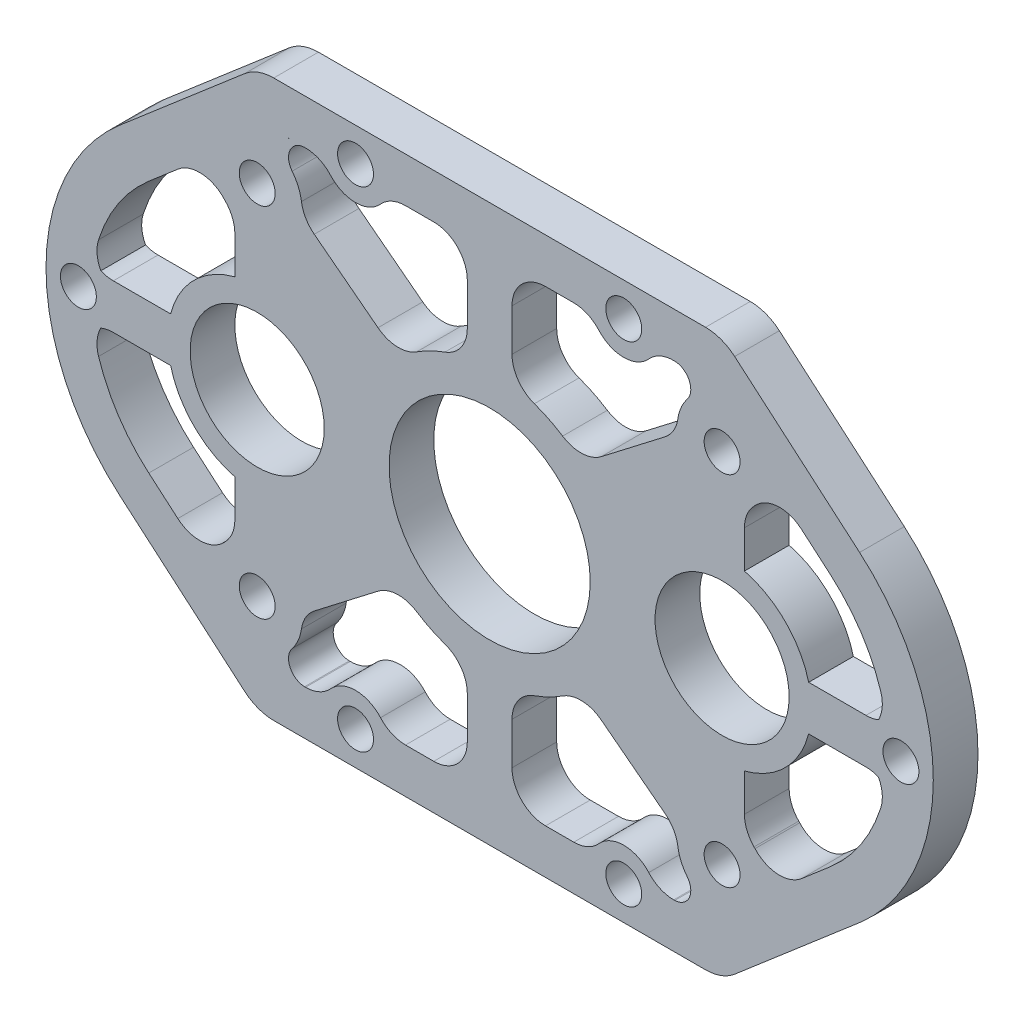
SolidWorks part; units mm, degrees
material "6061-T6 (SS)"
ref_plane "Front Plane" through (0, 0, 0) normal (0, 0, 1) x (1, 0, 0)
ref_plane "Top Plane" through (0, 0, 0) normal (0, 1, 0) x (1, 0, 0)
ref_plane "Right Plane" through (0, 0, 0) normal (1, 0, 0) x (0, 0, -1)
sketch "Sketch1" plane through (0, 0, 0) normal (0, 0, 1) x (1, 0, 0)
  line L0 (127, 25.4) -> (127, 0) construction
  line L1 (0, 0) -> (254, 0)
  line L2 (0, 0) -> (0, 25.4)
  line L3 (0, 25.4) -> (254, 25.4)
  line L4 (254, 0) -> (254, 25.4)
  line L18 (110.6338, 19.05) -> (106.9677, 12.7)
  line L19 (106.9677, 12.7) -> (110.6338, 6.35)
  line L20 (110.6338, 6.35) -> (117.9662, 6.35)
  line L21 (117.9662, 6.35) -> (121.6323, 12.7)
  line L22 (121.6323, 12.7) -> (117.9662, 19.05)
  line L23 (117.9662, 19.05) -> (110.6338, 19.05)
  circle A0 centre (81.28, 12.7) radius 30 construction
  circle A1 centre (147.32, 12.7) radius 30 construction
  circle A2 centre (81.28, 12.7) radius 7.62 construction
  circle A3 centre (147.32, 12.7) radius 8.636
  circle A4 centre (81.28, 12.7) radius 8.636
  circle A5 centre (147.32, 12.7) radius 7.62 construction
  circle A6 centre (114.3, 12.7) radius 25.4 construction
  circle A7 centre (114.3, 12.7) radius 26.67
  circle A8 centre (114.3, 12.7) radius 22.2377 construction
  circle A11 centre (114.3, 12.7) radius 6.35 construction
  point P46 (0, 12.7)
  dimension "D4" = 17.272
  dimension "D9" = 53.34
  dimension "D13" = 12.7
  dimension "D1" = 25.4
  dimension "D2" = 254
  dimension "D10" = 12.7
  dimension "D12" = 12.7
sketch "Sketch3" plane through (0, 0, 0) normal (0, 0, 1) x (1, 0, 0)
  line L0 (81.28, 42.7) -> (147.32, 42.7) construction
  line L5 (81.28, 12.7) -> (114.3, 12.7) construction
  line L6 (114.3, 12.7) -> (147.32, 12.7) construction
  line L9 (114.3, 42.7) -> (114.3, -17.3) construction
  line L10 (61.7477, 35.4704) -> (81.28, 52.225)
  line L25 (81.28, 52.225) -> (147.32, 52.225)
  line L26 (147.32, 52.225) -> (166.8523, 35.4704)
  line L27 (110.6338, 19.05) -> (106.9677, 12.7)
  line L28 (106.9677, 12.7) -> (110.6338, 6.35)
  line L29 (110.6338, 6.35) -> (117.9662, 6.35)
  line L30 (117.9662, 6.35) -> (121.6323, 12.7)
  line L31 (121.6323, 12.7) -> (117.9662, 19.05)
  line L32 (117.9662, 19.05) -> (110.6338, 19.05)
  line L33 (110.565, 18.9308) -> (106.9677, 12.7)
  line L34 (106.9677, 12.7) -> (110.6338, 6.35)
  line L35 (110.6338, 6.35) -> (117.9662, 6.35)
  line L36 (117.9662, 6.35) -> (121.6323, 12.7)
  line L37 (121.6323, 12.7) -> (117.9662, 19.05)
  line L38 (117.9662, 19.05) -> (110.6338, 19.05)
  line L39 (96.3395, 30.6605) -> (132.2605, -5.2605) construction
  line L40 (99.2405, 30.6605) -> (81.28, 12.7) construction
  line L41 (95.25, 47.4625) -> (133.35, 47.4625) construction
  line L42 (81.28, -17.3) -> (147.32, -17.3) construction
  line L43 (95.25, -22.0625) -> (133.35, -22.0625) construction
  line L44 (147.32, -26.825) -> (166.8523, -10.0704)
  line L45 (81.28, -26.825) -> (147.32, -26.825)
  line L46 (61.7477, -10.0704) -> (81.28, -26.825)
  line L47 (81.28, 12.7) -> (81.28, -12.7) construction
  line L48 (81.28, 12.7) -> (81.28, -12.7) construction
  line L49 (81.28, 12.7) -> (55.88, 12.7) construction
  circle A2 centre (81.28, 12.7) radius 30 construction
  circle A9 centre (114.3, 12.7) radius 26.67
  circle A10 centre (114.3, 12.7) radius 26.67 construction
  circle A11 centre (81.28, 12.7) radius 8.636
  circle A12 centre (81.28, 12.7) radius 8.636 construction
  circle A13 centre (147.32, 12.7) radius 8.636
  circle A16 centre (147.32, 12.7) radius 8.636 construction
  circle A17 centre (95.25, 47.4625) radius 2.5527
  circle A19 centre (114.3, 12.7) radius 25.4 construction
  circle A20 centre (114.3, 12.7) radius 22.2377 construction
  circle A22 centre (114.3, 12.7) radius 25.4 construction
  circle A23 centre (114.3, 12.7) radius 22.2377 construction
  arc A24 (108.3271, 25.6791) -> (108.3271, -0.2791) centre (81.28, 12.7) ccw
  circle A25 centre (114.3, 12.7) radius 14.2875
  circle A26 centre (81.28, 12.7) radius 9.525
  circle A27 centre (147.32, 12.7) radius 9.525
  circle A37 centre (133.35, 47.4625) radius 2.5527
  circle A38 centre (133.35, -22.0625) radius 2.5527
  circle A39 centre (95.25, -22.0625) radius 2.5527
  circle A40 centre (81.28, -12.7) radius 2.5527
  circle A41 centre (55.88, 12.7) radius 2.5527
  circle A42 centre (81.28, 38.1) radius 2.5527
  circle A43 centre (147.32, -12.7) radius 2.5527
  circle A44 centre (172.72, 12.7) radius 2.5527
  circle A45 centre (147.32, 38.1) radius 2.5527
  arc A47 (120.2729, -0.2791) -> (120.2729, 25.6791) centre (147.32, 12.7) ccw
  point P1 (0, 0)
  point P2 (114.3, 42.7)
  point P7 (0, 0)
  point P12 (0, 0)
  point P41 (114.3, 52.225)
  point P59 (114.3, 47.4625)
  point P69 (114.3, 12.7)
  point P78 (81.28, 12.7)
  point P84 (114.3, -22.0625)
  dimension "D3" = 45
  dimension "D4" = 9.525
  dimension "D2" = 45
  dimension "D8" = 25.4
  dimension "D14" = 28.575
  dimension "D15" = 19.05
  dimension "D16" = 3
  dimension "D5" = 5.1054
  dimension "D12" = 5.1054
  dimension "D7" = 4.7625
  dimension "D17" = 90
  dimension "2" = 50.8
  dimension "D6" = 19.05
  dimension "D9" = 0
  dimension "D10" = 0
  dimension "D11" = 0
  dimension "D13" = 0
extrude "Boss-Extrude1" add sketch "Sketch3" along normal blind 6.35 contours A24 A10 L26 L25 L10 A37 A17 | A24 L46 L45 L44 A10 A38 A39 | A10 A24 A12 A40 A42 | A23 A24 A25 | A23 A22 A12 | A22 A24 A10 A12 | A22 A12 A10 A24 | A24 A22 A23 | A24 A10 A22 | A22 A24 A23 | A25 A24 A23 | A25 A23 A24 | A24 A23 A22 | A24 A22 A10 | A23 A24 A22 | A23 A45 A25 A44 | A22 A45 A23 A44 A16 | A23 A45 A22 | A22 A45 A16 A10 | A10 A16 A43 | A22 A44 A23 | A22 A44 A10 A16 | A10 A26 A12 | A22 A12 A10 | A12 A22 | A10 A27 A16 | A16 A22 | A22 A16 A10 region at (81.1746, 41.9228, 0) region at (114.3, 45.5045, 0) region at (114.3, -20.1045, 0) region at (97.63, 12.7, 0) region at (114.3, 33.2042, 0) region at (114.3, -7.8042, 0) region at (147.4254, 41.9228, 0) region at (130.97, 12.7, 0)
fillet "Fillet2" radius 6.35 4 edges at (147.32, -26.825, 3.175) (81.28, -26.825, 3.175) (147.32, 52.225, 3.175) (81.28, 52.225, 3.175)
sketch "Sketch9" plane through (0, 0, 6.35) normal (0, 0, 1) x (1, 0, 0)
  line L0 (144.9696, -20.475) -> (162.7179, -5.2507)
  line L1 (162.7179, 30.6507) -> (144.9696, 45.875)
  line L2 (144.9696, 45.875) -> (83.6304, 45.875)
  line L3 (83.6304, 45.875) -> (65.8821, 30.6507)
  line L4 (65.8821, -5.2507) -> (83.6304, -20.475)
  line L5 (83.6304, -20.475) -> (144.9696, -20.475)
  line L6 (149.104, -25.2947) -> (166.8523, -10.0704)
  line L7 (166.8523, 35.4704) -> (149.104, 50.6947)
  line L8 (144.9696, 52.225) -> (83.6304, 52.225)
  line L9 (79.496, 50.6947) -> (61.7477, 35.4704)
  line L10 (61.7477, -10.0704) -> (79.496, -25.2947)
  line L11 (83.6304, -26.825) -> (144.9696, -26.825)
  line L12 (149.104, -25.2947) -> (166.8523, -10.0704)
  line L13 (166.8523, 35.4704) -> (149.104, 50.6947)
  line L14 (144.9696, 52.225) -> (83.6304, 52.225)
  line L15 (79.496, 50.6947) -> (61.7477, 35.4704)
  line L16 (61.7477, -10.0704) -> (79.496, -25.2947)
  line L17 (83.6304, -26.825) -> (144.9696, -26.825)
  line L18 (81.28, 38.1) -> (81.28, 12.7) construction
  line L19 (81.28, 12.7) -> (81.28, -12.7) construction
  line L20 (147.32, -12.7) -> (147.32, 12.7) construction
  line L21 (147.32, 12.7) -> (147.32, 38.1) construction
  line L22 (81.28, 12.7) -> (114.3, 12.7) construction
  line L23 (114.3, 12.7) -> (147.32, 12.7) construction
  line L24 (147.32, 12.7) -> (114.3, 12.7) construction
  line L25 (114.3, 12.7) -> (147.32, -12.7) construction
  line L26 (81.28, -12.7) -> (114.3, 12.7) construction
  line L27 (114.3, 12.7) -> (81.28, 38.1) construction
  line L28 (114.3, 12.7) -> (147.32, 38.1) construction
  line L29 (114.3, 12.7) -> (114.3, 45.875) construction
  line L30 (114.3, 12.7) -> (114.3, -20.475) construction
  line L31 (116.2358, 15.2166) -> (83.2158, 40.6166)
  line L32 (112.3642, 10.1834) -> (145.3842, -15.2166)
  line L33 (116.2358, 10.1834) -> (149.2558, 35.5834)
  line L34 (112.3642, 10.1834) -> (79.3442, 35.5834)
  line L35 (116.2358, 15.2166) -> (149.2558, -10.1834)
  line L36 (112.3642, 15.2166) -> (145.3842, 40.6166)
  line L37 (81.28, 12.7) -> (55.88, 12.7) construction
  line L38 (147.32, 12.7) -> (172.72, 12.7) construction
  line L39 (81.28, 9.525) -> (55.88, 9.525)
  line L40 (81.28, 9.525) -> (114.3, 9.525)
  line L41 (114.3, 9.525) -> (147.32, 9.525)
  line L42 (147.32, 9.525) -> (172.72, 9.525)
  line L43 (81.28, 15.875) -> (55.88, 15.875)
  line L44 (81.28, 15.875) -> (114.3, 15.875)
  line L45 (114.3, 15.875) -> (147.32, 15.875)
  line L46 (147.32, 15.875) -> (172.72, 15.875)
  line L47 (83.2158, -15.2166) -> (116.2358, 10.1834)
  line L48 (79.3442, -10.1834) -> (112.3642, 15.2166)
  line L49 (111.125, 12.7) -> (111.125, -20.475)
  line L50 (117.475, 12.7) -> (117.475, -20.475)
  line L51 (117.475, 12.7) -> (117.475, 45.875)
  line L52 (111.125, 12.7) -> (111.125, 45.875)
  line L53 (78.105, 38.1) -> (78.105, 12.7)
  line L54 (78.105, 12.7) -> (78.105, -12.7)
  line L55 (150.495, -12.7) -> (150.495, 12.7)
  line L56 (150.495, 12.7) -> (150.495, 38.1)
  line L57 (84.455, 38.1) -> (84.455, 12.7)
  line L58 (84.455, 12.7) -> (84.455, -12.7)
  line L59 (144.145, -12.7) -> (144.145, 12.7)
  line L60 (144.145, 12.7) -> (144.145, 38.1)
  circle A0 centre (55.88, 12.7) radius 4.6
  circle A1 centre (95.25, 47.4625) radius 4.7625
  arc A2 (166.8523, -10.0704) -> (166.8523, 35.4704) centre (147.32, 12.7) ccw
  arc A3 (61.7477, 35.4704) -> (61.7477, -10.0704) centre (81.28, 12.7) ccw
  arc A4 (166.8523, -10.0704) -> (166.8523, 35.4704) centre (147.32, 12.7) ccw
  arc A5 (61.7477, 35.4704) -> (61.7477, -10.0704) centre (81.28, 12.7) ccw
  circle A6 centre (133.35, 47.4625) radius 4.7625
  circle A7 centre (172.72, 12.7) radius 4.6
  circle A8 centre (133.35, -22.0625) radius 4.7625
  circle A9 centre (95.25, -22.0625) radius 4.7625
  circle A10 centre (81.28, 12.7) radius 9.525
  circle A11 centre (81.28, -12.7) radius 6.35
  circle A12 centre (81.28, 38.1) radius 6.35
  circle A13 centre (147.32, 38.1) radius 6.35
  circle A14 centre (147.32, 12.7) radius 9.525
  circle A15 centre (147.32, -12.7) radius 6.35
  arc A16 (144.9696, -26.825) -> (149.104, -25.2947) centre (144.9696, -20.475) ccw
  arc A17 (144.9696, -26.825) -> (149.104, -25.2947) centre (144.9696, -20.475) ccw
  arc A18 (149.104, 50.6947) -> (144.9696, 52.225) centre (144.9696, 45.875) ccw
  arc A19 (149.104, 50.6947) -> (144.9696, 52.225) centre (144.9696, 45.875) ccw
  arc A20 (83.6304, 52.225) -> (79.496, 50.6947) centre (83.6304, 45.875) ccw
  arc A21 (83.6304, 52.225) -> (79.496, 50.6947) centre (83.6304, 45.875) ccw
  arc A22 (79.496, -25.2947) -> (83.6304, -26.825) centre (83.6304, -20.475) ccw
  arc A23 (79.496, -25.2947) -> (83.6304, -26.825) centre (83.6304, -20.475) ccw
  arc A24 (162.7179, -5.2507) -> (162.7179, 30.6507) centre (147.32, 12.7) ccw
  arc A25 (144.9696, 45.875) -> (144.9696, 45.875) centre (144.9696, 45.875) ccw
  arc A26 (83.6304, 45.875) -> (83.6304, 45.875) centre (83.6304, 45.875) ccw
  arc A27 (65.8821, 30.6507) -> (65.8821, -5.2507) centre (81.28, 12.7) ccw
  arc A28 (83.6304, -20.475) -> (83.6304, -20.475) centre (83.6304, -20.475) ccw
  arc A29 (144.9696, -20.475) -> (144.9696, -20.475) centre (144.9696, -20.475) ccw
  circle A30 centre (114.3, 12.7) radius 19.05
  circle A32 centre (81.28, 12.7) radius 12.7
  circle A33 centre (147.32, 12.7) radius 12.7
  dimension "D2" = 19.05
  dimension "D3" = 12.7
  dimension "D4" = 38.1
  dimension "D18" = 25.4
  dimension "D17" = 6.35
  dimension "D1" = 0
  dimension "D5" = 3.175
  dimension "D6" = 3.175
  dimension "D7" = 3.175
  dimension "D8" = 3.175
  dimension "D9" = 3.175
  dimension "D10" = 3.175
  dimension "D11" = 3.175
  dimension "D12" = 3.175
  dimension "D13" = 3.175
  dimension "D14" = 3.175
  dimension "D15" = 3.175
  dimension "D16" = 3.175
extrude "Cut-Extrude2" cut sketch "Sketch9" against normal blind 6.35 contours A32 L53 A12 L3 A27 A0 L43 | A32 L39 A0 A27 L4 A11 L54 | A30 L52 L2 A1 L3 A12 L31 | A30 L36 A13 L1 L2 A6 L51 | A33 L46 A7 A24 L1 A13 L56 | A33 L55 A15 L0 A24 A7 L42 | A30 L50 L5 A8 L0 A15 L32 | A30 L47 A11 L4 L5 A9 L49 region at (128.7733, -12.6609, 6.35) region at (159.8487, -0.042, 6.35) region at (99.8267, -12.6609, 6.35) region at (159.8487, 25.442, 6.35) region at (68.7513, -0.042, 6.35) region at (128.7733, 38.0609, 6.35) region at (68.7513, 25.442, 6.35) region at (99.8267, 38.0609, 6.35)
fillet "Fillet3" radius 4.7625 48 edges at (117.475, 45.875, 3.175) (128.8599, 45.875, 3.175) (137.8401, 45.875, 3.175) (144.9696, 45.875, 3.175) (146.6698, 44.4166, 3.175) (141.0253, 37.2636, 3.175) (127.2525, 26.6691, 3.175) (117.475, 31.4836, 3.175) (101.3475, 26.6691, 3.175) (81.9302, 44.4166, 3.175) (83.6304, 45.875, 3.175) (90.7599, 45.875, 3.175) (99.7401, 45.875, 3.175) (111.125, 45.875, 3.175) (111.125, 31.4836, 3.175) (87.5747, 37.2636, 3.175) (111.125, -6.0836, 3.175) (111.125, -20.475, 3.175) (99.7401, -20.475, 3.175) (90.7599, -20.475, 3.175) (81.9302, -19.0166, 3.175) (87.5747, -11.8636, 3.175) (101.3475, -1.2691, 3.175) (83.6304, -20.475, 3.175) (127.2525, -1.2691, 3.175) (141.0253, -11.8636, 3.175) (146.6698, -19.0166, 3.175) (144.9696, -20.475, 3.175) (137.8401, -20.475, 3.175) (128.8599, -20.475, 3.175) (117.475, -6.0836, 3.175) (117.475, -20.475, 3.175) (169.3914, 15.875, 3.175) (150.495, 32.6007, 3.175) (153.662, 38.4188, 3.175) (170.6137, 16.7895, 3.175) (78.105, 32.6007, 3.175) (59.2086, 15.875, 3.175) (74.938, 38.4188, 3.175) (57.9863, 16.7895, 3.175) (78.105, -7.2007, 3.175) (74.938, -13.0188, 3.175) (57.9863, 8.6105, 3.175) (59.2086, 9.525, 3.175) (150.495, -7.2007, 3.175) (153.662, -13.0188, 3.175) (169.3914, 9.525, 3.175) (170.6137, 8.6105, 3.175)
sketch "Sketch11" plane through (0, 0, 6.35) normal (0, 0, 1) x (1, 0, 0)
  line L4 (53.3273, 12.7) -> (175.2727, 12.7) construction
  line L5 (114.3, 52.225) -> (114.3, -26.825) construction
  line L6 (83.6304, 52.225) -> (144.9696, 52.225) construction
  line L7 (83.6304, -26.825) -> (144.9696, -26.825) construction
  line L16 (143.3237, -20.4736) -> (140.4495, -20.475)
  line L17 (143.3237, 45.8736) -> (140.4495, 45.875)
  line L18 (85.2763, 45.8736) -> (88.1505, 45.875)
  line L19 (85.3931, -20.475) -> (88.1505, -20.475) construction
  line L20 (85.3931, -20.475) -> (88.1505, -20.475)
  circle A1 centre (55.88, 12.7) radius 2.5527 construction
  circle A3 centre (172.72, 12.7) radius 2.5527 construction
  arc A17 (86.2424, -16.662) -> (88.1505, -20.475) centre (88.0778, -18.1274) ccw
  arc A18 (86.2424, -16.662) -> (87.568, -13.5855) centre (81.28, -12.7) ccw construction
  arc A19 (86.2424, -16.662) -> (85.2763, -20.4736) centre (89.9642, -19.6335) ccw construction
  arc A21 (142.3576, -16.662) -> (143.3237, -20.4736) centre (138.6358, -19.6335) cw
  arc A22 (142.3576, -16.662) -> (140.4495, -20.475) centre (140.5222, -18.1274) cw
  arc A23 (142.3576, 42.062) -> (140.4495, 45.875) centre (140.5222, 43.5274) ccw
  arc A24 (142.3576, 42.062) -> (143.3237, 45.8736) centre (138.6358, 45.0335) ccw
  arc A25 (86.2424, 42.062) -> (85.2763, 45.8736) centre (89.9642, 45.0335) cw
  arc A26 (86.2424, 42.062) -> (88.1505, 45.875) centre (88.0778, 43.5274) cw
  arc A27 (85.2763, -20.4736) -> (85.3931, -20.475) centre (85.3931, -15.7125) ccw construction
  arc A28 (85.2763, -20.4736) -> (85.3931, -20.475) centre (85.3931, -15.7125) ccw
  arc A29 (86.2424, -16.662) -> (85.2763, -20.4736) centre (89.9642, -19.6335) ccw
extrude "Boss-Extrude3" add sketch "Sketch11" against normal up to surface (6.35 mm away) contours A17 A29 A28 L20 | A21 A22 L16 | A25 A26 L18 | A23 A24 L17 | L17 A23 A24 region at (142.7262, -19.5499, 6.35) region at (142.7262, 44.9499, 6.35) region at (85.8738, 44.9499, 6.35) region at (85.8741, -19.5506, 6.35) up to face at (96.993, 39.8725, 0)
equation "\"NEO\"= 60mm"
equation "\"D3@Sketch1\"=\"NEO\""
equation "\"D5@Sketch1\"=\"NEO\""
